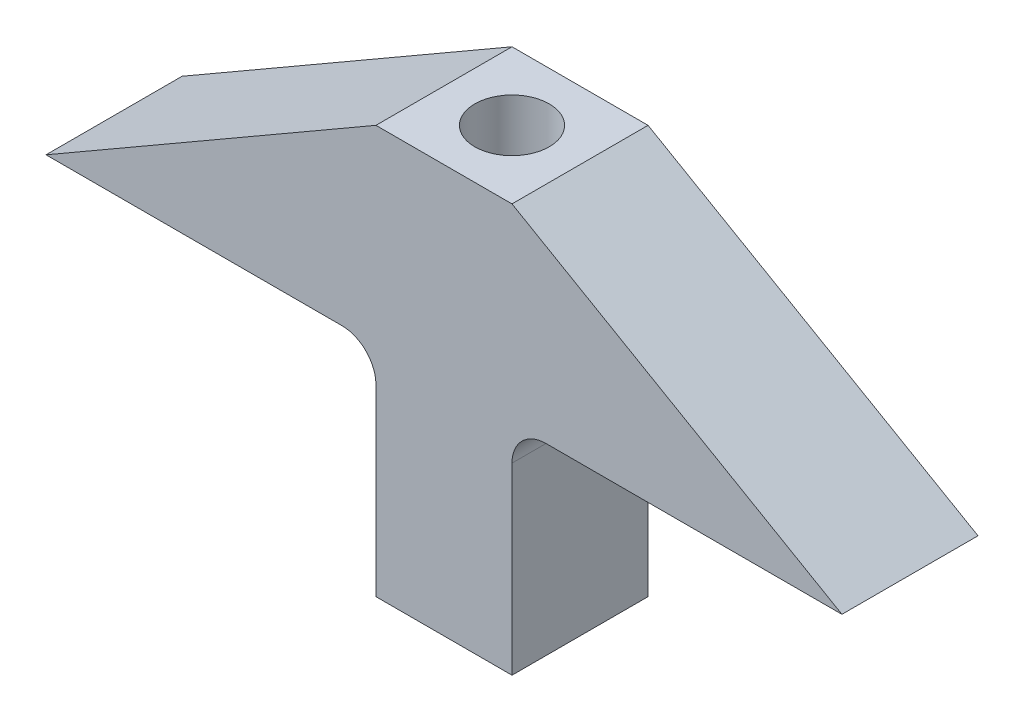
SolidWorks part; units mm, degrees
material "6061-T6 (SS)"
ref_plane "Front Plane" through (0, 0, 0) normal (0, 0, 1) x (1, 0, 0)
ref_plane "Top Plane" through (0, 0, 0) normal (0, 1, 0) x (1, 0, 0)
ref_plane "Right Plane" through (0, 0, 0) normal (1, 0, 0) x (0, 0, -1)
sketch "Sketch1" plane through (0, 0, 0) normal (0, 0, 1) x (1, 0, 0)
  line L0 (0, 0) -> (61.5917, 0)
  line L1 (148.5835, 0) -> (86.9917, 35.56)
  line L2 (86.9917, 35.56) -> (61.5917, 35.56)
  line L3 (61.5917, 35.56) -> (0, 0)
  line L4 (61.5917, 0) -> (61.5917, -40.64)
  line L5 (61.5917, -40.64) -> (86.9917, -40.64)
  line L6 (86.9917, -40.64) -> (86.9917, 0)
  line L7 (86.9917, 0) -> (148.5835, 0)
  point P8 (74.2917, -40.64)
  point P10 (74.2917, 35.56)
  dimension "D1" = 30
  dimension "D2" = 30
  dimension "D3" = 25.4
  dimension "D4" = 35.56
  dimension "D5" = 76.2
  dimension "D6" = 25.4
extrude "Boss-Extrude1" add sketch "Sketch1" along normal blind 25.4
hole_wizard "35/64 (0.54688) Diameter Hole1" positions "Sketch2" profile "Sketch3" hole size "35/64" standard "ANSI Inch"
sketch "Sketch2" plane through (0, 35.56, 0) normal (0, 1, 0) x (1, 0, 0)
  point P0 (74.2917, -12.7)
  dimension "D1" = 12.7
  dimension "D2" = 12.7
sketch "Sketch3" plane through (74.2917, 35.56, 12.7) normal (1, 0, 0) x (0, 0, 1)
  line L0 (0, 0) -> (0, 39.2252)
  line L1 (0, 39.2252) -> (6.9454, 35.052)
  line L2 (6.9454, 35.052) -> (6.9454, 0)
  line L5 (6.9454, 0) -> (0, 0)
  line L10 (0, 39.2252) -> (-6.9454, 35.052) construction
  line L11 (0, -6.35) -> (0, 107.95) construction
  dimension "Hole Dia." = 13.8908
  dimension "Hole Depth" = 35.052
  dimension "Drill Angle" = 118
hole_wizard "#10-32 Tapped Hole1" positions "Sketch4" profile "Sketch5" tap size "#10-32" standard "ANSI Inch"
sketch "Sketch4" plane through (0, -40.64, 0) normal (0, -1, 0) x (-1, 0, 0)
  point P0 (-77.4667, -15.875)
  point P3 (-71.1167, -9.525)
  dimension "D1" = 9.525
  dimension "D2" = 9.525
  dimension "D3" = 9.525
  dimension "D4" = 9.525
sketch "Sketch5" plane through (77.4667, -40.64, 15.875) normal (1, 0, 0) x (0, 0, -1)
  line L0 (0, 0) -> (0, 9.8493)
  line L1 (0, 9.8493) -> (2.0193, 8.636)
  line L2 (2.0193, 8.636) -> (2.0193, 0)
  line L5 (2.0193, 0) -> (0, 0)
  line L10 (0, 9.8493) -> (-2.0193, 8.636) construction
  line L11 (0, -6.35) -> (0, 107.95) construction
  dimension "Tap Drill Dia." = 4.0386
  dimension "Tap Drill Depth" = 8.636
  dimension "Drill Angle" = 118
cosmetic thread "Hole Thread1" parameters "D1"=6.35, "D2"=4.826
cosmetic thread "Hole Thread2" parameters "D1"=6.35, "D2"=4.826
fillet "Fillet1" radius 6.35 2 edges at (86.9917, 0, 12.7) (61.5917, 0, 12.7)
